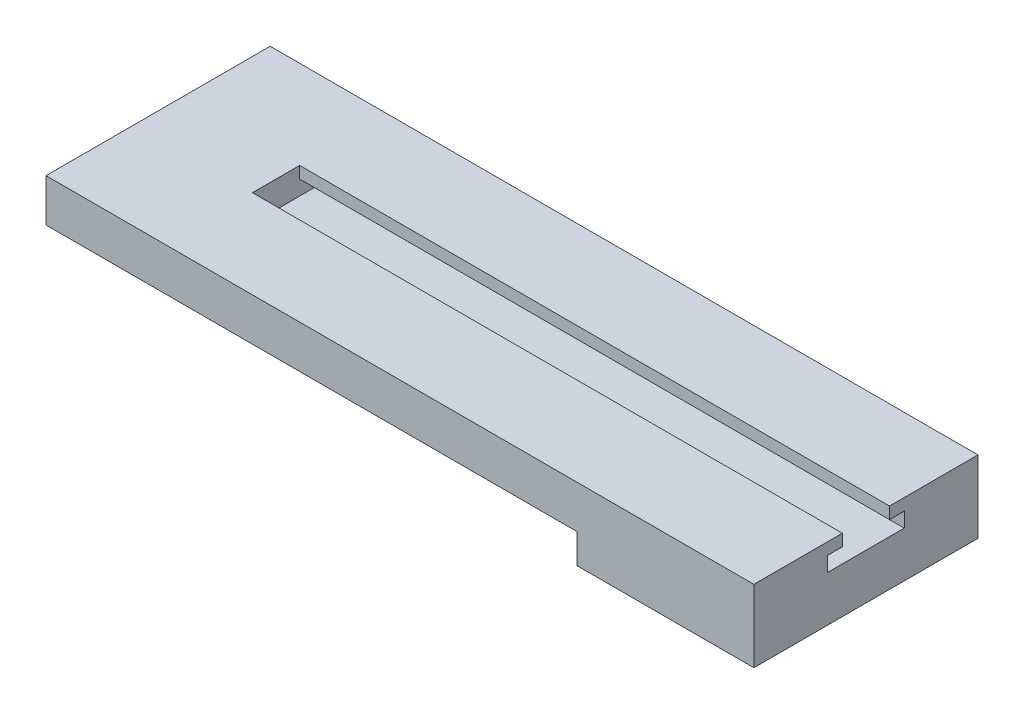
SolidWorks part; units mm, degrees
ref_plane "Front Plane" through (0, 0, 0) normal (0, 0, 1) x (1, 0, 0)
ref_plane "Top Plane" through (0, 0, 0) normal (0, 1, 0) x (1, 0, 0)
ref_plane "Right Plane" through (0, 0, 0) normal (1, 0, 0) x (0, 0, -1)
sketch "Sketch1" plane through (0, 0, 0) normal (0, 1, 0) x (1, 0, 0)
  line L0 (0, 0) -> (200, 0)
  line L1 (0, 0) -> (0, -16)
  line L2 (0, -16) -> (200, -16)
  line L3 (200, -16) -> (200, -46)
  line L4 (200, -46) -> (-40, -46)
  line L5 (-40, -46) -> (-40, 30)
  line L6 (-40, 30) -> (200, 30)
  line L7 (200, 30) -> (200, 0)
  dimension "D1" = 200
  dimension "D2" = 16
  dimension "D3" = 30
  dimension "D4" = 240
  dimension "D5" = 76
extrude "Boss-Extrude1" add sketch "Sketch1" along normal blind 4
sketch "Sketch2" plane through (0, 0, 0) normal (0, 1, 0) x (1, 0, 0)
  line L0 (209.7303, -8) -> (-59.5425, -8) construction
  line L1 (200, -8) -> (200, 5) construction
  line L2 (200, 5) -> (0, 5)
  line L3 (0, 5) -> (0, -21)
  line L4 (200, 5) -> (200, 30)
  line L5 (200, 30) -> (-40, 30)
  line L6 (-40, 30) -> (-40, -46)
  line L7 (-40, 30) -> (-40, -46) construction
  line L8 (200, -21) -> (200, -46)
  line L9 (200, -21) -> (0, -21)
  line L10 (200, -46) -> (-40, -46)
  point P18 (0, -8)
  point P19 (-40, -8)
  dimension "D1" = 13
extrude "Boss-Extrude2" add sketch "Sketch2" against normal blind 5
sketch "Sketch3" plane through (0, 0, 0) normal (0, 1, 0) x (1, 0, 0)
  line L0 (-40, 30) -> (200, 30)
  line L1 (200, 30) -> (200, -46)
  line L2 (200, -46) -> (-40, -46)
  line L3 (-40, -46) -> (-40, 30)
extrude "Boss-Extrude3" add sketch "Sketch3" against normal blind 5.5 from offset 5 offset against normal yes
sketch "Sketch4" plane through (0, 0, 0) normal (0, 1, 0) x (1, 0, 0)
  line L0 (200, 30) -> (200, -46)
  line L1 (200, -46) -> (140, -46)
  line L2 (-40, -46) -> (200, -46) construction
  line L3 (140, -46) -> (140, 30)
  line L4 (200, 30) -> (-40, 30) construction
  line L5 (140, 30) -> (200, 30)
  dimension "D1" = 60
extrude "Boss-Extrude4" add sketch "Sketch4" against normal blind 10 from offset 10.5 contours L5 L0 L1 L3 offset against normal yes
sketch "Sketch5" plane through (0, 0, 0) normal (0, 1, 0) x (1, 0, 0)
  line L0 (170, -46) -> (170, 30) construction
  line L3 (200, -8) -> (140, -8) construction
  line L6 (170, -8) -> (170, -23) construction
  line L7 (170, -23) -> (172.5, -23)
  line L8 (170, -23) -> (167.5, -23)
  line L9 (167.5, -23) -> (167.5, -10)
  line L10 (167.5, -10) -> (162.5, -10)
  line L11 (162.5, -10) -> (162.5, -6)
  line L12 (177.5, -10) -> (177.5, -6)
  line L13 (172.5, -10) -> (177.5, -10)
  line L14 (172.5, -23) -> (172.5, -10)
  line L15 (172.5, -6) -> (177.5, -6)
  line L16 (172.5, 7) -> (172.5, -6)
  line L17 (170, 7) -> (172.5, 7)
  line L18 (170, 7) -> (167.5, 7)
  line L19 (167.5, 7) -> (167.5, -6)
  line L20 (167.5, -6) -> (162.5, -6)
  point P15 (177.5, -8)
  point P21 (162.5, -8)
  dimension "D1" = 15
  dimension "D3" = 2.5
  dimension "D5" = 5
extrude "Cut-Extrude1" cut sketch "Sketch5" along normal blind 8 from offset 21 offset against normal yes
